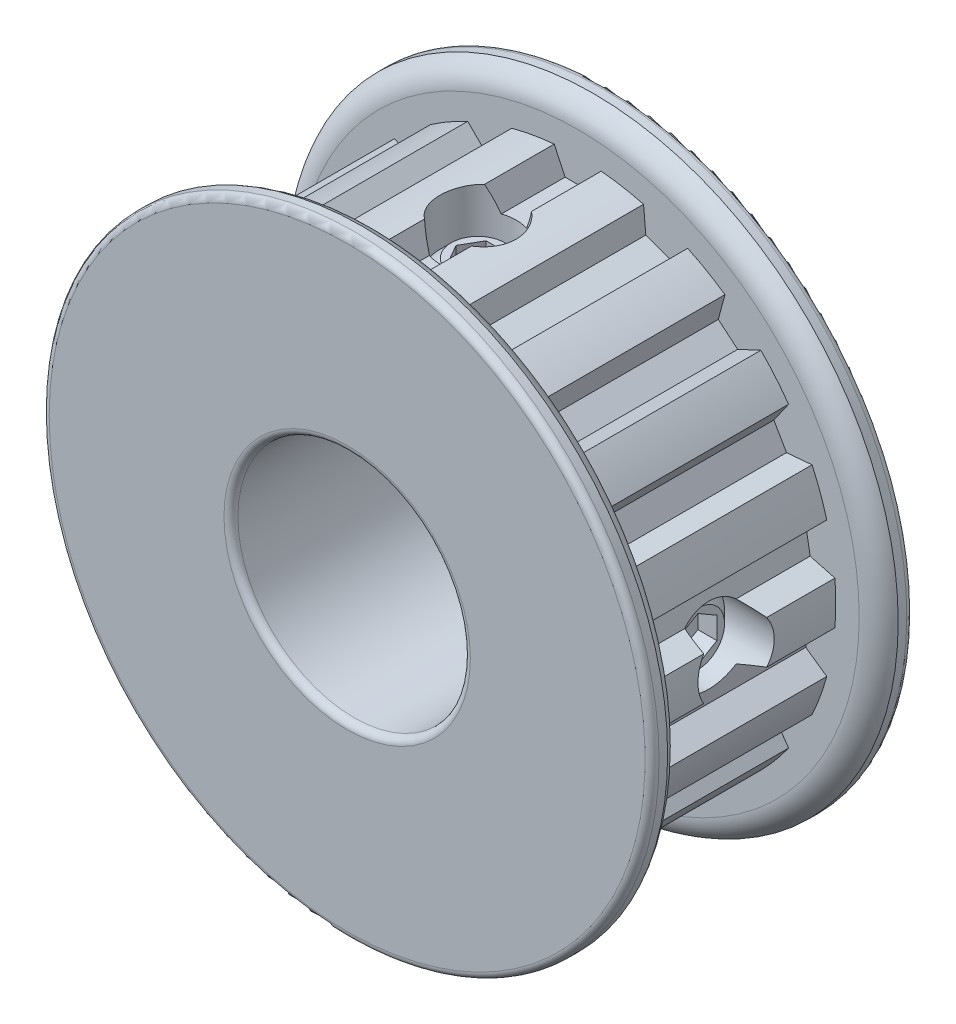
SolidWorks part; units mm, degrees
note: '?' marks a value the reader was unsure of.
ref_plane "Front Plane" through (0, 0, 0) normal (0, 0, 1) x (1, 0, 0)
ref_plane "Top Plane" through (0, 0, 0) normal (0, 1, 0) x (1, 0, 0)
ref_plane "Right Plane" through (0, 0, 0) normal (1, 0, 0) x (0, 0, -1)
sketch "Sketch1" plane through (0, 0, 0) normal (0, 0, 1) x (1, 0, 0)
  line L0 (-1.2827, 14.0462) -> (-0.6905, 12.7762)
  line L1 (-0.6905, 12.7762) -> (0.6905, 12.7762)
  line L2 (0.6905, 12.7762) -> (1.2827, 14.0462)
  line L3 (-1.2827, 14.0462) -> (1.2827, 14.0462)
  line L4 (0, 0) -> (0, 12.7762) construction
  line L5 (0, 12.7762) -> (0, 15.0622) construction
  circle A0 centre (0, 0) radius 14.5542 construction
  circle A1 centre (0, 0) radius 16.6624 construction
  circle A2 centre (0, 0) radius 14.1046 construction
  point P6 (0, 14.0462)
  point P11 (0, 14.5542)
  point P13 (0, 16.6624)
  point P14 (0, 14.1046)
  dimension "D1" = 1.016
  dimension "PD" = 29.1084
  dimension "D2" = 0.508
  dimension "OD" = 33.3248
  dimension "b" = 50
  dimension "bt" = 2.5654
  dimension "ht" = 1.27
  dimension "hs" = 2.286
sketch "Sketch2" plane through (0, 0, 0) normal (1, 0, 0) x (0, 0, -1)
  line L0 (-7.1501, 6.35) -> (7.1501, 6.35)
  line L3 (-7.1501, 6.35) -> (-7.1501, 16.6624)
  line L4 (-7.1501, 16.6624) -> (-5.4483, 16.6624) construction
  line L5 (-5.4483, 16.6624) -> (-5.4483, 14.1046) construction
  line L6 (-5.4483, 14.1046) -> (5.4483, 14.1046)
  line L7 (5.4483, 14.1046) -> (5.4483, 16.6624) construction
  line L8 (5.4483, 16.6624) -> (7.1501, 16.6624) construction
  line L9 (7.1501, 16.6624) -> (7.1501, 6.35)
  line L10 (-7.1501, 0) -> (7.1501, 0) construction
  line L13 (-7.1501, 16.6624) -> (-6.2992, 16.6624)
  line L14 (-5.4483, 15.3835) -> (-5.4483, 14.1046)
  line L15 (5.4483, 14.1046) -> (5.4483, 15.3835)
  line L16 (6.2992, 16.6624) -> (7.1501, 16.6624)
  arc A0 (-5.4483, 15.3835) -> (-6.2992, 16.6624) centre (-6.8348, 15.3835) ccw
  arc A1 (5.4483, 15.3835) -> (6.2992, 16.6624) centre (6.8348, 15.3835) cw
  point P12 (-5.4483, 15.3835)
  point P14 (-6.2992, 16.6624)
  point P20 (5.4483, 15.3835)
  point P21 (6.2992, 16.6624)
  point P25 (5.4483, 0)
  point P26 (-5.4483, 0)
  dimension "OA" = 14.3002
  dimension "Bore" = 12.7
  dimension "Outside Width" = 14.3002
  dimension "Inside Width" = 10.8966
revolve "Revolve1" add sketch "Sketch2" angle 360 mid plane about L10
sketch "Sketch3" plane through (0, 0, 0) normal (0, 0, 1) x (1, 0, 0)
  line L0 (-0.6905, 12.7762) -> (0.6905, 12.7762) construction
  line L1 (0.6905, 12.7762) -> (1.2827, 14.0462) construction
  line L2 (-1.2827, 14.0462) -> (-0.6905, 12.7762) construction
  line L3 (-0.6905, 12.7762) -> (0.6905, 12.7762)
  line L4 (0.6905, 12.7762) -> (1.2827, 14.0462)
  line L5 (-1.2827, 14.0462) -> (-0.6905, 12.7762)
  circle A0 centre (0, 0) radius 14.1046 construction
  arc A1 (1.2827, 14.0462) -> (-1.2827, 14.0462) centre (0, 0) ccw
extrude "Cut-Extrude1" cut sketch "Sketch3" against normal up to vertex (5.4483 mm away) from vertex at 5.4483 starting at point (0, 14.1046, 5.4483)
pattern_circular "CirPattern1" count 18 over 360 about axis through (0, 0, 0) along (0, 0, 1) of "Cut-Extrude1"
fillet "Fillet1" radius 0.381 4 edges at (6.35, 0, -7.1501) (16.6624, 0, -7.1501) (16.6624, 0, 7.1501) (6.35, 0, 7.1501)
sketch "Sketch5" plane through (0, 0, 0) normal (0, 1, 0) x (1, 0, 0)
  line L1 (1.2827, 0) -> (-1.2827, 0) construction
  line L2 (1.2827, 5.4483) -> (1.2827, -5.4483) construction
  line L3 (-1.2827, 5.4483) -> (-1.2827, -5.4483) construction
  circle A0 centre (0, 0) radius 2.0828
extrude "Cut-Extrude2" cut sketch "Sketch5" along normal through all
sketch "Sketch6" plane through (0, 0, 0) normal (1, 0, 0) x (0, 0, -1)
  line L0 (0, 12.0142) -> (0, 7.112)
  line L1 (6.7691, 6.35) -> (-6.7691, 6.35) construction
  line L3 (2.0828, 12.7762) -> (-2.0828, 12.7762) construction
  line L4 (-1.965, 12.7762) -> (-2.0828, 12.7762) construction
  line L5 (2.0828, 12.7762) -> (1.965, 12.7762) construction
  line L6 (0, 12.0142) -> (-1.458, 12.0142)
  line L7 (-1.458, 12.0142) -> (-2.0828, 11.3894)
  line L8 (-2.0828, 11.3894) -> (-2.0828, 7.7368)
  line L9 (-2.0828, 7.7368) -> (-1.458, 7.112)
  line L10 (-1.458, 7.112) -> (0, 7.112)
  point P12 (0, 6.35)
  point P19 (0, 12.7762)
  dimension "D1" = 0.762
  dimension "D2" = 0.762
  dimension "D3" = 135
  dimension "D4" = 0.6248
revolve "Revolve2" add sketch "Sketch6" angle 360 about L0
sketch "Sketch7" plane through (0, 12.0142, 0) normal (0, 1, 0) x (1, 0, 0)
  line L1 (1.2025, 0) -> (0.6013, 1.0414)
  line L2 (0.6013, 1.0414) -> (-0.6013, 1.0414)
  line L3 (-0.6013, 1.0414) -> (-1.2025, 0)
  line L4 (-1.2025, 0) -> (-0.6013, -1.0414)
  line L5 (-0.6013, -1.0414) -> (0.6013, -1.0414)
  line L6 (0.6013, -1.0414) -> (1.2025, 0)
  circle A0 centre (0, 0) radius 1.0414 construction
  dimension "D1" = 2.0828
extrude "Cut-Extrude3" cut sketch "Sketch7" against normal blind 1.0414
pattern_circular "CirPattern2" count 2 over 270 about axis through (0, 0, 0) along (0, 0, 1) of "Cut-Extrude2", "Revolve2", "Cut-Extrude3"
ref_axis "Center Axis 1" through (0, 0, -6.7691) along (0, 0, 1)?
ref_plane "Contact Plane 1" through (0, 0, 7.1501) normal (0, 0, 1) x (1, 0, 0)
ref_plane "Contact Plane 2" through (0, 0, -7.1501) normal (0, 0, -1) x (-1, 0, 0)
equation "\"D4@Sketch6\" = \"Set Screw Dia@Sketch5\" * .15"
equation "\"D1@Sketch7\" = \"Set Screw Dia@Sketch5\" / 2"
equation "\"D1@Cut-Extrude3\" = \"Set Screw Dia@Sketch5\" / 4"
